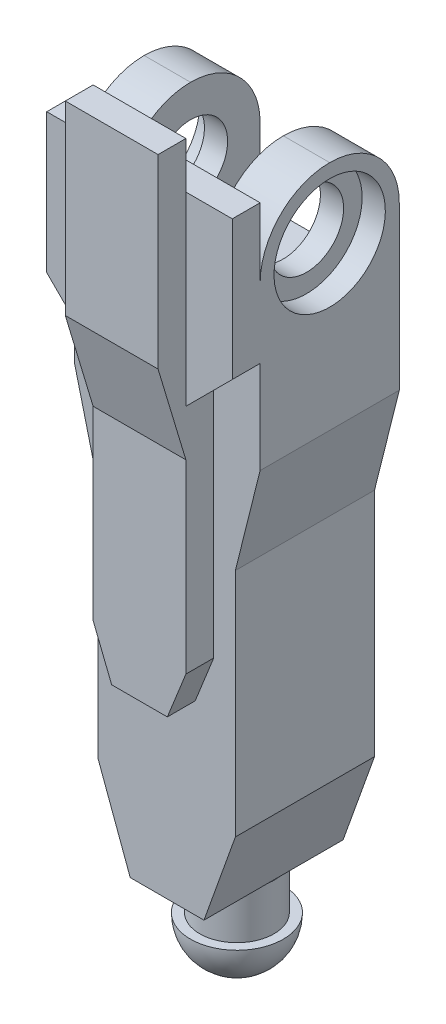
SolidWorks part; units mm, degrees
ref_plane "Front Plane" through (0, 0, 0) normal (0, 0, 1) x (1, 0, 0)
ref_plane "Top Plane" through (0, 0, 0) normal (0, 1, 0) x (1, 0, 0)
ref_plane "Right Plane" through (0, 0, 0) normal (1, 0, 0) x (0, 0, -1)
sketch "Sketch1" plane through (0, 0, 0) normal (0, 0, 1) x (1, 0, 0)
  line L0 (4.0016, 29.5717) -> (4.0016, 14.5717)
  line L1 (-10.9984, 29.5717) -> (-5.9984, 29.5717)
  line L2 (-10.9984, 29.5717) -> (-10.9984, -40.4283)
  line L3 (-10.9984, -40.4283) -> (9.0016, -40.4283)
  line L4 (9.0016, 29.5717) -> (9.0016, -40.4283)
  line L7 (4.0016, 29.5717) -> (9.0016, 29.5717)
  line L8 (4.0016, 14.5717) -> (-5.9984, 14.5717)
  line L9 (-5.9984, 29.5717) -> (-5.9984, 14.5717)
  dimension "D1" = 70
  dimension "D2" = 20
  dimension "D3" = 5
  dimension "D4" = 5
  dimension "D5" = 15
extrude "Boss-Extrude2" add sketch "Sketch1" along normal blind 15 contours L2 L3 L4 L7 L0 L8 L9 L1
sketch "Sketch2" plane through (-10.9984, 0, 0) normal (-1, 0, 0) x (0, 0, 1)
  line L0 (15, 14.5717) -> (0, 14.5717)
  line L1 (15, 29.5717) -> (15, -40.4283) construction
  line L2 (0, 29.5717) -> (0, -40.4283) construction
  line L3 (15, 29.5717) -> (0, 29.5717) construction
  circle A0 centre (7.5, 22.0717) radius 4
  dimension "D2" = 8
  dimension "D1" = 15
extrude "Cut-Extrude1" cut sketch "Sketch2" against normal blind 20 contours A0 region at (-10.9984, 22.0717, 7.5)
sketch "Sketch3" plane through (-10.9984, 0, 0) normal (-1, 0, 0) x (0, 0, 1)
  circle A0 centre (7.5, 22.0717) radius 6
extrude "Cut-Extrude2" cut sketch "Sketch3" against normal blind 2.5
sketch "Sketch4" plane through (9.0016, 0, 0) normal (1, 0, 0) x (0, 0, -1)
  circle A0 centre (-7.5, 22.0717) radius 6
extrude "Cut-Extrude3" cut sketch "Sketch4" against normal blind 2.5
fillet "Fillet1" radius 7.5 4 edges at (6.5016, 29.5717, 0) (6.5016, 29.5717, 15) (-8.4984, 29.5717, 0) (-8.4984, 29.5717, 15)
sketch "Sketch5" plane through (0, 0, 15) normal (0, 0, 1) x (1, 0, 0)
  line L2 (-5.9984, 9.5717) -> (-5.9984, -15.4283)
  line L4 (4.0016, 9.5717) -> (4.0016, -15.4283)
  line L5 (9.0016, 22.0717) -> (9.0016, -40.4283) construction
  line L6 (-5.9984, -15.4283) -> (-3.9984, -20.4283)
  line L9 (-3.9984, -20.4283) -> (2.0016, -20.4283)
  line L11 (4.0016, -15.4283) -> (2.0016, -20.4283)
  line L12 (-10.9984, 29.5717) -> (9.0016, 29.5717)
  line L13 (-10.9984, 29.5717) -> (-10.9984, 14.5488)
  line L15 (9.0016, 29.5717) -> (9.0016, 14.5717)
  line L16 (-10.9984, 14.5488) -> (-5.9984, 9.5717)
  line L18 (4.0016, 9.5717) -> (9.0016, 14.5717)
  dimension "D1" = 5
extrude "Boss-Extrude3" add sketch "Sketch5" along normal blind 3
sketch "Sketch6" plane through (0, 0, 18) normal (0, 0, 1) x (1, 0, 0)
  line L0 (4.0016, -15.4283) -> (4.0016, 9.5717) construction
  line L1 (-5.9984, 34.5717) -> (4.0016, 34.5717)
  line L2 (-5.9984, 34.5717) -> (-5.9984, 4.5717)
  line L3 (-5.9984, 4.5717) -> (4.0016, 4.5717)
  line L4 (4.0016, 34.5717) -> (4.0016, 4.5717)
  line L5 (9.0016, 29.5717) -> (-10.9984, 29.5717) construction
  dimension "D1" = 10
  dimension "D2" = 30
  dimension "D3" = 5
extrude "Boss-Extrude4" add sketch "Sketch6" along normal blind 3
sketch "Sketch7" plane through (-5.9984, 0, 0) normal (-1, 0, 0) x (0, 0, 1)
  line L2 (21, 34.5717) -> (21, 4.5717) construction
  line L3 (21, 14.5488) -> (18, 4.5717)
  line L4 (18, 4.5717) -> (21, 4.5717)
  line L5 (21, 4.5717) -> (21, 14.5488)
extrude "Cut-Extrude4" cut sketch "Sketch7" against normal blind 10
sketch "Sketch8" plane through (0, -40.4283, 0) normal (0, -1, 0) x (1, 0, 0)
  circle A0 centre (-0.9984, 7.5) radius 4
  dimension "D1" = 8
extrude "Boss-Extrude6" add sketch "Sketch8" along normal blind 5
sketch "Sketch9" plane through (0, -45.4283, 0) normal (0, -1, 0) x (-1, 0, 0)
  line L1 (0.9984, -12.5) -> (0.9984, -2.5)
  arc A2 (0.9984, -12.5) -> (0.9984, -2.5) centre (0.9984, -7.5) ccw
  dimension "D1" = 5
revolve "Revolve3" add sketch "Sketch9" angle 180 about L1 reverse direction yes
sketch "Sketch10" plane through (0, 0, 15) normal (0, 0, 1) x (1, 0, 0)
  line L1 (-10.9984, 14.5488) -> (-10.9984, -40.4283) construction
  line L3 (-8.4984, -5.4283) -> (-8.4984, -24.4153)
  line L4 (-8.4984, -24.4153) -> (-8.4984, -30.9672)
  line L5 (-8.4984, -30.9672) -> (-4.9984, -40.4283)
  line L6 (-4.9984, -40.4283) -> (2.9495, -40.4283)
  line L7 (-10.9984, -40.4283) -> (9.0016, -40.4283) construction
  line L8 (2.9495, -40.4283) -> (6.3356, -30.9672)
  line L9 (6.3356, -30.9672) -> (6.3356, -6.0924)
  line L10 (-10.9984, 4.5717) -> (-10.9984, -40.4283)
  line L11 (-10.9984, 4.5717) -> (-10.9984, -40.4283)
  line L12 (9.0016, 14.5717) -> (9.0016, -40.4283) construction
  line L13 (-10.9984, -40.4283) -> (9.0016, -40.4283)
  line L14 (9.0016, -40.4283) -> (9.0016, 4.5717)
  line L15 (-10.9984, 4.5717) -> (-8.4984, -5.4283)
  line L16 (-5.9984, -15.4283) -> (4.0016, -15.4283)
  line L17 (6.3356, -6.0924) -> (9.0016, 4.5717)
  line L18 (9.0016, -40.4283) -> (9.0016, 4.5717)
  line M18 (-10.9984, 14.5488) -> (-10.9984, -40.4283)
  line M19 (-10.9984, -40.4283) -> (9.0016, -40.4283)
  line M20 (9.0016, -40.4283) -> (9.0016, 14.5717)
extrude "Cut-Extrude6" cut sketch "Sketch10" against normal blind 15 contours L17 L9 L8 M19 M20 | L15 L5 L4 L3 M18 M19 region at (7.3966, -22.6847, 15) region at (-9.4498, -22.732, 15)
